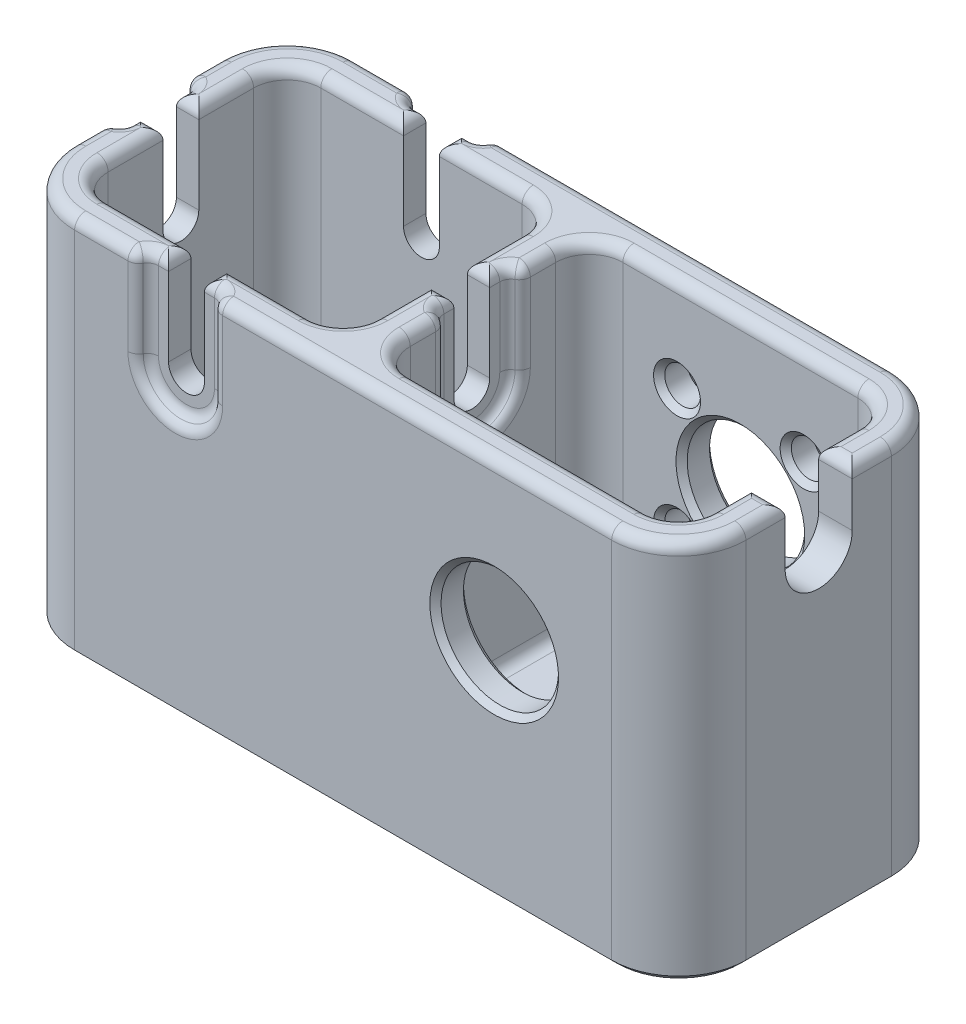
SolidWorks part; units mm, degrees
ref_plane "Front Plane" through (0, 0, 0) normal (0, 0, 1) x (1, 0, 0)
ref_plane "Top Plane" through (0, 0, 0) normal (0, 1, 0) x (1, 0, 0)
ref_plane "Right Plane" through (0, 0, 0) normal (1, 0, 0) x (0, 0, -1)
sketch "Sketch1" plane through (0, 0, 0) normal (0, 1, 0) x (1, 0, 0)
  line L1 (0, 0) -> (60, 0)
  line L2 (0, 0) -> (0, 25)
  line L3 (0, 25) -> (60, 25)
  line L4 (60, 0) -> (60, 25)
  dimension "D1" = 25
  dimension "D2" = 60
extrude "Boss-Extrude1" add sketch "Sketch1" along normal blind 4
sketch "Sketch3" plane through (0, 4, 0) normal (0, 1, 0) x (1, 0, 0)
  line L0 (0, 25) -> (0, 0) construction
  line L1 (60, 25) -> (0, 25) construction
  circle A0 centre (7.5, 17.5) radius 1.6
  circle A1 centre (22.5, 17.5) radius 1.6
  circle A2 centre (22.5, 7.5) radius 1.6
  circle A3 centre (7.5, 7.5) radius 1.6
  dimension "D1" = 3.2
  dimension "D2" = 10
  dimension "D3" = 15
  dimension "D4" = 7.5
  dimension "D5" = 7.5
extrude "Cut-Extrude1" cut sketch "Sketch3" against normal through all
sketch "Sketch4" plane through (0, 4, 0) normal (0, 1, 0) x (1, 0, 0)
  line L0 (27, 22) -> (27, 3)
  line L1 (0, 25) -> (60, 25)
  line L2 (0, 25) -> (0, 0)
  line L3 (0, 0) -> (60, 0)
  line L4 (60, 25) -> (60, 0)
  line L5 (3, 22) -> (27, 22)
  line L6 (3, 22) -> (3, 3)
  line L7 (3, 3) -> (27, 3)
  line L8 (57, 22) -> (57, 3)
  line L9 (30, 22) -> (30, 3)
  line L10 (30, 22) -> (57, 22)
  line L11 (30, 3) -> (57, 3)
  dimension "D1" = 3
  dimension "D2" = 3
  dimension "D3" = 3
  dimension "D4" = 3
  dimension "D5" = 24
  dimension "D6" = 3
extrude "Boss-Extrude2" add sketch "Sketch4" along normal blind 30
sketch "Sketch5" plane through (0, 0, -25) normal (0, 0, -1) x (-1, 0, 0)
  line L0 (-60, 0) -> (0, 0) construction
  line L1 (-57, 34) -> (-30, 34) construction
  circle A0 centre (-43.5, 20) radius 5.25
  point P8 (-43.5, 34)
  dimension "D1" = 10.5
  dimension "D2" = 20
extrude "Cut-Extrude2" cut sketch "Sketch5" against normal through all
sketch "Sketch6" plane through (0, 0, -25) normal (0, 0, -1) x (-1, 0, 0)
  line L0 (-37.8431, 14.3431) -> (-49.1569, 25.6569) construction
  line L1 (-49.1569, 14.3431) -> (-37.8431, 25.6569) construction
  line L2 (-43.5, 14.75) -> (-43.5, 25.25) construction
  line L3 (-38.25, 20) -> (-48.75, 20) construction
  circle A0 centre (-37.8431, 14.3431) radius 1.6
  circle A1 centre (-49.1569, 14.3431) radius 1.6
  circle A2 centre (-49.1569, 25.6569) radius 1.6
  circle A3 centre (-37.8431, 25.6569) radius 1.6
  circle A5 centre (-43.5, 20) radius 5.25 construction
  point P16 (-43.5, 20)
  point P17 (-43.5, 20)
  dimension "D3" = 3.2
  dimension "D1" = 90
  dimension "D2" = 8
extrude "Cut-Extrude3" cut sketch "Sketch6" against normal up to next
fillet "Fillet3" radius 3 8 edges at (30, 19, -3) (57, 19, -3) (27, 19, -3) (3, 19, -3) (3, 19, -22) (27, 19, -22) (57, 19, -22) (30, 19, -22)
fillet "Fillet4" radius 1 16 edges at (56.1213, 4, -3.8787) (43.5, 4, -3) (30.8787, 4, -3.8787) (30, 4, -12.5) (30.8787, 4, -21.1213) (43.5, 4, -22) (56.1213, 4, -21.1213) (26.1213, 4, -3.8787) (15, 4, -3) (3.8787, 4, -3.8787) (3, 4, -12.5) (3.8787, 4, -21.1213) (15, 4, -22) (26.1213, 4, -21.1213) (57, 4, -12.5) (27, 4, -12.5)
fillet "Fillet5" radius 6 4 edges at (60, 17, 0) (60, 17, -25) (0, 17, 0) (0, 17, -25)
sketch "Sketch7" plane through (0, 0, -25) normal (0, 0, -1) x (-1, 0, 0)
  line L0 (-13.4, 26) -> (-13.4, 34)
  line L1 (-54, 34) -> (-6, 34) construction
  line L2 (-13.4, 34) -> (-16.6, 34)
  line L3 (-16.6, 34) -> (-16.6, 26)
  line L5 (-24, 34) -> (-6, 34) construction
  arc A0 (-16.6, 26) -> (-13.4, 26) centre (-15, 26) ccw
  point P1 (-15, 34)
  point P10 (-15, 34)
  dimension "D1" = 1.6
  dimension "D2" = 8
extrude "Cut-Extrude4" cut sketch "Sketch7" against normal through all
sketch "Sketch8" plane through (0, 0, 0) normal (-1, 0, 0) x (0, 0, 1)
  line L0 (-14.1, 26) -> (-14.1, 34)
  line L1 (-19, 34) -> (-6, 34) construction
  line L2 (-14.1, 34) -> (-10.9, 34)
  line L3 (-10.9, 34) -> (-10.9, 26)
  line L4 (-19, 34) -> (-6, 34) construction
  arc A0 (-14.1, 26) -> (-10.9, 26) centre (-12.5, 26) ccw
  point P1 (-12.5, 34)
  point P10 (-12.5, 34)
  dimension "D2" = 1.6
  dimension "D1" = 8
extrude "Cut-Extrude5" cut sketch "Sketch8" against normal up to surface (30 mm away) up to face at (30, 19.5, -12.5)
sketch "Sketch9" plane through (60, 0, 0) normal (1, 0, 0) x (0, 0, -1)
  line L0 (15.5, 29) -> (15.5, 34)
  line L1 (6, 34) -> (19, 34) construction
  line L2 (15.5, 34) -> (9.5, 34)
  line L3 (9.5, 34) -> (9.5, 29)
  line L4 (6, 34) -> (19, 34) construction
  arc A0 (9.5, 29) -> (15.5, 29) centre (12.5, 29) ccw
  point P1 (12.5, 34)
  point P10 (12.5, 34)
  dimension "D2" = 3
  dimension "D1" = 5
extrude "Cut-Extrude6" cut sketch "Sketch9" against normal up to next
chamfer "Chamfer1" distance 0.5 angle 45 12 edges at (58.2426, 0, -23.2426) (30, 0, -25) (1.7574, 0, -23.2426) (0, 0, -12.5) (1.7574, 0, -1.7574) (30, 0, 0) (58.2426, 0, -1.7574) (60, 0, -12.5) (7.5, 0, -15.9) (22.5, 0, -15.9) (22.5, 0, -5.9) (7.5, 0, -5.9)
chamfer "Chamfer2" distance 0.5 angle 45 12 edges at (38.25, 20, -3) (38.25, 20, 0) (50.7569, 25.6569, -22) (50.7569, 14.3431, -22) (39.4431, 14.3431, -22) (48.75, 20, -22) (39.4431, 25.6569, -22) (36.2431, 25.6569, -25) (47.5569, 25.6569, -25) (47.5569, 14.3431, -25) (38.25, 20, -25) (36.2431, 14.3431, -25)
chamfer "Chamfer4" distance 0.5 angle 45 4 edges at (7.5, 4, -5.9) (22.5, 4, -5.9) (22.5, 4, -15.9) (7.5, 4, -15.9)
sketch "Sketch10" plane through (0, 0, -25) normal (0, 0, -1) x (-1, 0, 0)
  line L0 (-11.5, 26) -> (-11.5, 34)
  line L1 (-13.4, 34) -> (-6, 34) construction
  line L2 (-11.5, 34) -> (-18.5, 34)
  line L3 (-54, 34) -> (-16.6, 34) construction
  line L4 (-18.5, 34) -> (-18.5, 26)
  arc A0 (-18.5, 26) -> (-11.5, 26) centre (-15, 26) ccw
  dimension "D1" = 7
extrude "Cut-Extrude7" cut sketch "Sketch10" against normal blind 1
sketch "Sketch11" plane through (0, 0, 0) normal (0, 0, 1) x (1, 0, 0)
  line L0 (11.5, 26) -> (11.5, 34)
  line L1 (6, 34) -> (13.4, 34) construction
  line L2 (11.5, 34) -> (18.5, 34)
  line L3 (16.6, 34) -> (54, 34) construction
  line L4 (18.5, 34) -> (18.5, 26)
  arc A0 (11.5, 26) -> (18.5, 26) centre (15, 26) ccw
  dimension "D1" = 3.5
extrude "Cut-Extrude8" cut sketch "Sketch11" against normal blind 1
sketch "Sketch12" plane through (0, 0, 0) normal (-1, 0, 0) x (0, 0, 1)
  line L0 (-16, 26) -> (-16, 34)
  line L1 (-19, 34) -> (-14.1, 34) construction
  line L2 (-16, 34) -> (-9, 34)
  line L3 (-10.9, 34) -> (-6, 34) construction
  line L4 (-9, 34) -> (-9, 26)
  arc A0 (-16, 26) -> (-9, 26) centre (-12.5, 26) ccw
  dimension "D1" = 3.5
extrude "Cut-Extrude9" cut sketch "Sketch12" against normal blind 1
sketch "Sketch13" plane through (30, 0, 0) normal (1, 0, 0) x (0, 0, -1)
  line L0 (9, 26) -> (9, 34)
  line L1 (10.9, 34) -> (6, 34) construction
  line L2 (9, 34) -> (16, 34)
  line L3 (19, 34) -> (14.1, 34) construction
  line L4 (16, 34) -> (16, 26)
  arc A0 (9, 26) -> (16, 26) centre (12.5, 26) ccw
  dimension "D1" = 3.5
extrude "Cut-Extrude10" cut sketch "Sketch13" against normal blind 1
fillet "Fillet6" radius 1 12 edges at (18.5, 30, -24) (15, 22.5, -24) (1, 30, -9) (1, 22.5, -12.5) (29, 30, -9) (29, 22.5, -12.5) (18.5, 30, -1) (15, 22.5, -1) (11.5, 30, -24) (1, 30, -16) (29, 30, -16) (11.5, 30, -1)
fillet "Fillet7" radius 1 12 edges at (30, 30, -9) (30, 22.5, -12.5) (11.5, 30, -25) (15, 22.5, -25) (0, 30, -16) (0, 22.5, -12.5) (18.5, 30, 0) (15, 22.5, 0) (30, 30, -16) (18.5, 30, -25) (0, 30, -9) (11.5, 30, 0)
fillet "Fillet8" radius 1 60 edges at (2, 34, -10.9) (3, 34, -8.45) (3.8787, 34, -3.8787) (9.7, 34, -3) (13.4, 34, -2) (12, 34, -0.866) (11.2679, 34, -0.134) (8.384, 34, 0) (1.7574, 34, -1.7574) (0, 34, -7.134) (0.134, 34, -8.7679) (0.866, 34, -9.5) (13.4, 34, -23) (9.7, 34, -22) (3.8787, 34, -21.1213) (3, 34, -16.55) (2, 34, -14.1) (0.866, 34, -15.5) (0.134, 34, -16.2321) (0, 34, -17.866) (1.7574, 34, -23.2426) (8.384, 34, -25) (11.2679, 34, -24.866) (12, 34, -24.134) (28, 34, -14.1) (27, 34, -16.55) (26.1213, 34, -21.1213) (20.3, 34, -22) (16.6, 34, -23) (18, 34, -24.134) (18.7321, 34, -24.866) (36.616, 34, -25) (58.2426, 34, -23.2426) (60, 34, -17.25) (58.5, 34, -15.5) (57, 34, -17.25) (56.1213, 34, -21.1213) (43.5, 34, -22) (30.8787, 34, -21.1213) (30, 34, -17.866) (29.866, 34, -16.2321) (29.134, 34, -15.5) (30.8787, 34, -3.8787) (43.5, 34, -3) (56.1213, 34, -3.8787) (57, 34, -7.75) (58.5, 34, -9.5) (60, 34, -7.75) (58.2426, 34, -1.7574) (36.616, 34, 0) (18.7321, 34, -0.134) (18, 34, -0.866) (16.6, 34, -2) (20.3, 34, -3) (26.1213, 34, -3.8787) (27, 34, -8.45) (28, 34, -10.9) (29.134, 34, -9.5) (29.866, 34, -8.7679) (30, 34, -7.134)
